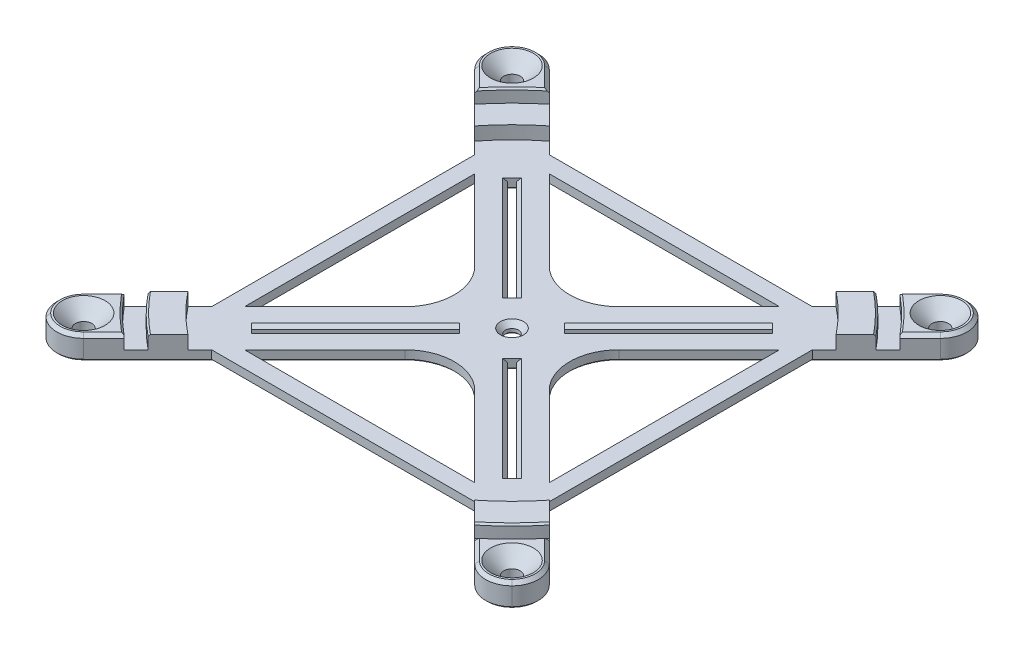
SolidWorks part; units mm, degrees
ref_plane "Спереди" through (0, 0, 0) normal (0, 0, 1) x (1, 0, 0)
ref_plane "Сверху" through (0, 0, 0) normal (0, 1, 0) x (1, 0, 0)
ref_plane "Справа" through (0, 0, 0) normal (1, 0, 0) x (0, 0, -1)
sketch "Эскиз1" plane through (0, 0, 0) normal (0, 1, 0) x (1, 0, 0)
  line L0 (-147.5, 147.5) -> (147.5, -147.5) construction
  line L1 (-147.5, -147.5) -> (147.5, -147.5) construction
  line L2 (-147.5, -147.5) -> (-147.5, 147.5) construction
  line L3 (-147.5, 147.5) -> (147.5, 147.5) construction
  line L4 (147.5, -147.5) -> (147.5, 147.5) construction
  line L5 (0, 147.5) -> (0, -147.5) construction
  line L6 (-147.5, 0) -> (147.5, 0) construction
  line L7 (130.1076, -152.7351) -> (-152.7351, 130.1076)
  line L8 (130.1076, -152.7351) -> (152.7351, -130.1076)
  line L9 (-152.7351, 130.1076) -> (-130.1076, 152.7351)
  line L10 (152.7351, -130.1076) -> (-130.1076, 152.7351)
  circle A0 centre (0, 0) radius 157.5 construction
  point P0 (0, 0)
  point P5 (-374.2756, 135.5581)
  point P6 (0, 0)
  point P9 (147.0611, -147.0611)
  dimension "D5" = 32
  dimension "D1" = 295
  dimension "D2" = 295
  dimension "D3" = 400
  dimension "D4" = 45
extrude "Бобышка-Вытянуть1" add sketch "Эскиз1" along normal blind 14
sketch "Эскиз2" plane through (0, 0, 0) normal (0, 1, 0) x (1, 0, 0)
  line L0 (0, 0) -> (189.3234, 0) construction
  line L1 (0, 0) -> (209.4677, 209.4677) construction
  line L2 (-152.7351, -130.1076) -> (130.1076, 152.7351)
  line L3 (-152.7351, -130.1076) -> (-130.1076, -152.7351)
  line L4 (130.1076, 152.7351) -> (152.7351, 130.1076)
  line L5 (-130.1076, -152.7351) -> (152.7351, 130.1076)
  line L6 (-152.7351, -130.1076) -> (152.7351, 130.1076) construction
  line L7 (130.1076, 152.7351) -> (-130.1076, -152.7351) construction
  point P3 (141.4214, 141.4214)
  dimension "D1" = 32
  dimension "D2" = 400
  dimension "D3" = 45
extrude "Бобышка-Вытянуть2" add sketch "Эскиз2" along normal blind 14
fillet "Скругление1" radius 16 8 edges at (-130.1076, 7, -152.7351) (-152.7351, 7, -130.1076) (130.1076, 7, 152.7351) (152.7351, 7, 130.1076) (-130.1076, 7, 152.7351) (-152.7351, 7, 130.1076) (130.1076, 7, -152.7351) (152.7351, 7, -130.1076)
sketch "Эскиз3" plane through (0, 14, 0) normal (0, 1, 0) x (1, 0, 0)
  line L1 (-130, -130) -> (130, -130) construction
  line L2 (-130, -130) -> (-130, 130) construction
  line L3 (-130, 130) -> (130, 130) construction
  line L4 (130, -130) -> (130, 130) construction
  line L5 (0, 130) -> (0, -130) construction
  line L6 (-130, 0) -> (130, 0) construction
  circle A0 centre (-130, -130) radius 5
  circle A1 centre (-130, 130) radius 5
  circle A2 centre (130, 130) radius 5
  circle A3 centre (130, -130) radius 5
  circle A4 centre (0, 0) radius 4
  point P0 (0, 0)
  point P14 (0, 0)
  dimension "D1" = 10
  dimension "D3" = 8
  dimension "D2" = 260
extrude "Вырез-Вытянуть1" cut sketch "Эскиз3" against normal through all
fillet "Скругление2" radius 30 4 edges at (22.6274, 7, 0) (0, 7, 22.6274) (-22.6274, 7, 0) (0, 7, -22.6274)
sketch "Эскиз4" plane through (0, 14, 0) normal (0, 1, 0) x (1, 0, 0)
  circle A0 centre (0, 0) radius 157
  dimension "D1" = 314
extrude "Вырез-Вытянуть-Тонкостенный1" cut sketch "Эскиз4" against normal blind 8 thin thin type one direction wall 10.2
chamfer "Фаска2" distance 1 angle 45 8 edges at (118.2283, 14, 118.2283) (111.0158, 14, 111.0158) (-111.0158, 14, -111.0158) (-118.2283, 14, -118.2283) (118.2283, 14, -118.2283) (111.0158, 14, -111.0158) (-111.0158, 14, 111.0158) (-118.2283, 14, 118.2283)
sketch "Эскиз5" plane through (0, 14, 0) normal (0, 1, 0) x (1, 0, 0)
  circle A0 centre (0, 0) radius 140
  dimension "D1" = 280
extrude "Вырез-Вытянуть2" cut sketch "Эскиз5" against normal blind 8
chamfer "Фаска3" distance 8 angle 45 4 edges at (-130, 14, -125) (130, 14, 135) (130, 14, -125) (-130, 14, 135)
chamfer "Фаска4" distance 2 angle 45 16 edges at (-112.9381, 14, -135.5655) (-130.1076, 14, -146.1076) (-135.5655, 14, -112.9381) (-146.1076, 14, -130.1076) (112.9381, 14, -135.5655) (135.5655, 14, -112.9381) (130.1076, 14, -146.1076) (146.1076, 14, -130.1076) (-135.5655, 14, 112.9381) (-146.1076, 14, 130.1076) (-112.9381, 14, 135.5655) (-130.1076, 14, 146.1076) (112.9381, 14, 135.5655) (130.1076, 14, 146.1076) (135.5655, 14, 112.9381) (146.1076, 14, 130.1076)
chamfer "Фаска5" distance 3 angle 45 1 edges at (0, 6, 4)
sketch "Эскиз8" plane through (0, 6, 0) normal (0, 1, 0) x (1, 0, 0)
  line L0 (0, 149.0517) -> (0, 0) construction
  line L1 (0, 0) -> (158.0685, 158.0685) construction
  line L2 (14.5163, 17.3447) -> (77.659, 80.4874)
  line L3 (14.5163, 17.3447) -> (17.3447, 14.5163)
  line L4 (77.659, 80.4874) -> (80.4874, 77.659)
  line L5 (17.3447, 14.5163) -> (80.4874, 77.659)
  line L6 (14.5163, 17.3447) -> (80.4874, 77.659) construction
  line L7 (77.659, 80.4874) -> (17.3447, 14.5163) construction
  line L8 (17.3447, -14.5163) -> (80.4874, -77.659)
  line L9 (17.3447, -14.5163) -> (14.5163, -17.3447)
  line L10 (14.5163, -17.3447) -> (77.659, -80.4874)
  line L11 (80.4874, -77.659) -> (77.659, -80.4874)
  line L12 (-14.5163, -17.3447) -> (-77.659, -80.4874)
  line L13 (-14.5163, -17.3447) -> (-17.3447, -14.5163)
  line L14 (-17.3447, -14.5163) -> (-80.4874, -77.659)
  line L15 (-77.659, -80.4874) -> (-80.4874, -77.659)
  line L16 (-17.3447, 14.5163) -> (-80.4874, 77.659)
  line L17 (-17.3447, 14.5163) -> (-14.5163, 17.3447)
  line L18 (-14.5163, 17.3447) -> (-77.659, 80.4874)
  line L19 (-80.4874, 77.659) -> (-77.659, 80.4874)
  point P5 (47.5019, 47.5019)
  point P24 (0, 0)
  dimension "D1" = 4
  dimension "D2" = 45
extrude "Вырез-Вытянуть4" cut sketch "Эскиз8" against normal through all
chamfer "Фаска6" distance 2 angle 45 8 edges at (-46.0877, 6, 48.9161) (-48.9161, 6, 46.0877) (48.9161, 6, -46.0877) (46.0877, 6, -48.9161) (46.0877, 6, 48.9161) (48.9161, 6, 46.0877) (-48.9161, 6, -46.0877) (-46.0877, 6, -48.9161)
sketch "Эскиз9" plane through (0, 6, 0) normal (0, 1, 0) x (1, 0, 0)
  line L0 (-86.1627, 102.497) -> (86.4506, 102.497)
  line L1 (-86.1627, 102.497) -> (-86.1627, 92.497)
  line L2 (86.4506, 102.497) -> (86.4506, 92.497)
  line L3 (-86.1627, 92.497) -> (86.4506, 92.497)
  line L4 (-86.1627, 102.497) -> (86.4506, 92.497) construction
  line L5 (86.4506, 102.497) -> (-86.1627, 92.497) construction
  line L6 (102.497, 86.1627) -> (102.497, -86.4506)
  line L7 (102.497, 86.1627) -> (92.497, 86.1627)
  line L8 (92.497, 86.1627) -> (92.497, -86.4506)
  line L9 (102.497, -86.4506) -> (92.497, -86.4506)
  line L10 (86.1627, -102.497) -> (-86.4506, -102.497)
  line L11 (86.1627, -102.497) -> (86.1627, -92.497)
  line L12 (86.1627, -92.497) -> (-86.4506, -92.497)
  line L13 (-86.4506, -102.497) -> (-86.4506, -92.497)
  line L14 (-102.497, -86.1627) -> (-102.497, 86.4506)
  line L15 (-102.497, -86.1627) -> (-92.497, -86.1627)
  line L16 (-92.497, -86.1627) -> (-92.497, 86.4506)
  line L17 (-102.497, 86.4506) -> (-92.497, 86.4506)
  point P1 (0.1439, 97.497)
  point P20 (0, 0)
  dimension "D1" = 10
extrude "Бобышка-Вытянуть3" add sketch "Эскиз9" against normal blind 6
chamfer "Фаска7" distance 1 angle 45 57 edges at (0, 0, 35.0538) (99.3317, 0, 121.9592) (45.5414, 0, 68.1688) (130.1076, 0, 146.1076) (146.1076, 0, 130.1076) (121.9592, 0, 99.3317) (68.1688, 0, 45.5414) (35.0538, 0, 0) (121.9592, 0, -99.3317) (68.1688, 0, -45.5414) (146.1076, 0, -130.1076) (130.1076, 0, -146.1076) (99.3317, 0, -121.9592) (45.5414, 0, -68.1688) (0, 0, -35.0538) (-99.3317, 0, -121.9592) (-45.5414, 0, -68.1688) (-130.1076, 0, -146.1076) (-146.1076, 0, -130.1076) (-68.1688, 0, -45.5414) (-121.9592, 0, -99.3317) (-35.0538, 0, 0) (-68.1688, 0, 45.5414) (-121.9592, 0, 99.3317) (-146.1076, 0, 130.1076) (-130.1076, 0, 146.1076) (-99.3317, 0, 121.9592) (-45.5414, 0, 68.1688) (79.0732, 0, -79.0732) (48.9161, 0, -46.0877) (15.9305, 0, -15.9305) (46.0877, 0, -48.9161) (79.0732, 0, 79.0732) (46.0877, 0, 48.9161) (15.9305, 0, 15.9305) (48.9161, 0, 46.0877) (-79.0732, 0, 79.0732) (-48.9161, 0, 46.0877) (-15.9305, 0, 15.9305) (-46.0877, 0, 48.9161) (-79.0732, 0, -79.0732) (-46.0877, 0, -48.9161) (-15.9305, 0, -15.9305) (-48.9161, 0, -46.0877) (-130, 0, 135) (0, 0, 4) (-130, 0, -125) (130, 0, -125) (130, 0, 135) (0, 0, -92.497) (92.497, 0, 0) (0, 0, 92.497) (0, 0, 102.497) (102.497, 0, 0) (0, 0, -102.497) (-102.497, 0, 0) (-92.497, 0, 0)
